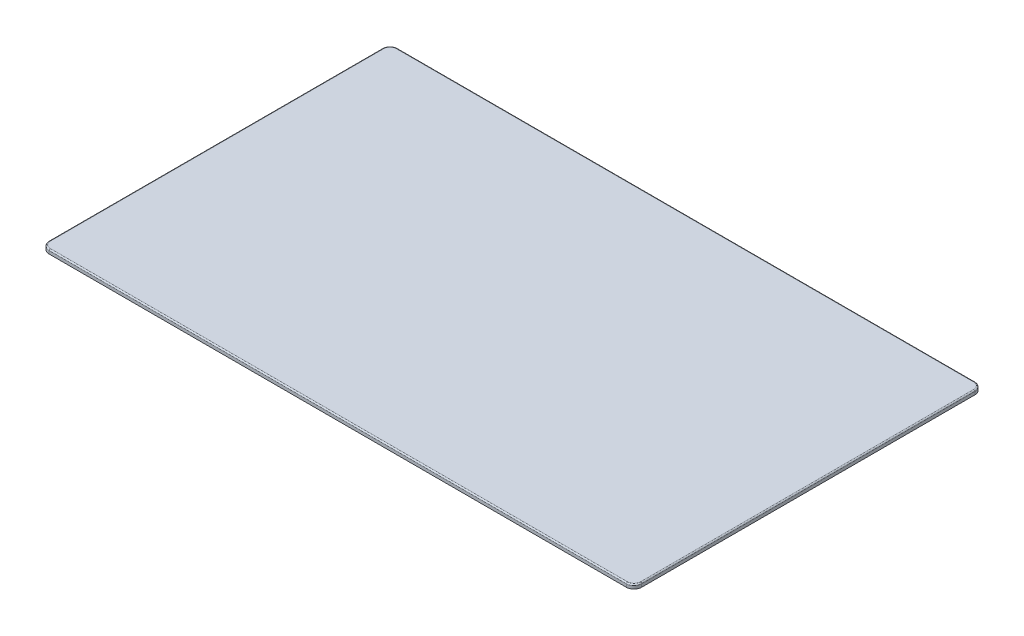
SolidWorks part; units mm, degrees
ref_plane "Ebene vorne" through (0, 0, 0) normal (0, 0, 1) x (1, 0, 0)
ref_plane "Ebene oben" through (0, 0, 0) normal (0, 1, 0) x (1, 0, 0)
ref_plane "Ebene rechts" through (0, 0, 0) normal (1, 0, 0) x (0, 0, -1)
sketch "Sketch1" plane through (0, 0, 0) normal (0, 1, 0) x (1, 0, 0)
  line L1 (-425, -250) -> (425, -250)
  line L2 (-425, -250) -> (-425, 250)
  line L3 (-425, 250) -> (425, 250)
  line L4 (425, -250) -> (425, 250)
  line L5 (-425, -250) -> (425, 250) construction
  line L6 (-425, 250) -> (425, -250) construction
  point P0 (0, 0)
  dimension "D1" = 500
  dimension "D2" = 850
extrude "Boss-Extrude1" add sketch "Sketch1" along normal blind 6
fillet "Fillet1" radius 1.75 4 edges at (0, 6, -250) (425, 6, 0) (-425, 6, 0) (0, 6, 250)
fillet "Fillet2" radius 11 8 edges at (-424.4874, 5.4874, 249.4874) (-425, 2.125, 250) (-424.4874, 5.4874, -249.4874) (424.4874, 5.4874, -249.4874) (424.4874, 5.4874, 249.4874) (425, 2.125, 250) (425, 2.125, -250) (-425, 2.125, -250)
